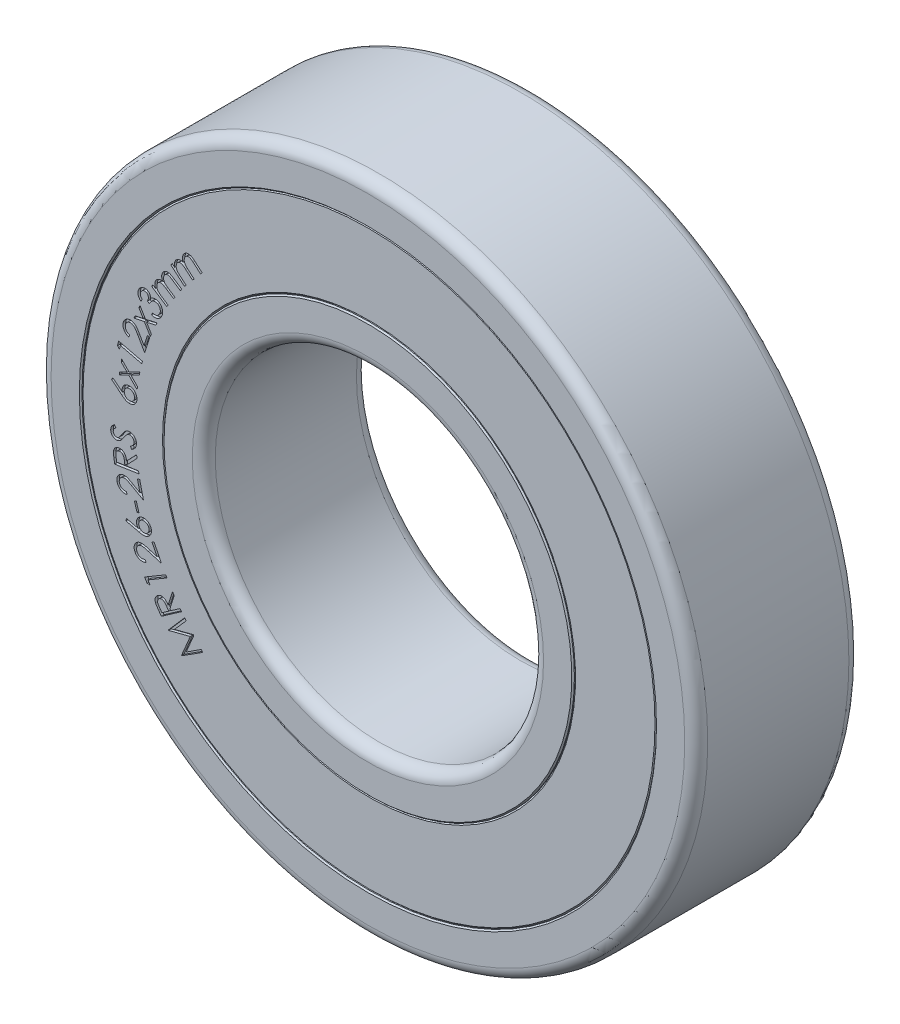
SolidWorks part; units mm, degrees
material "AISI 316 Annealed Stainless Steel Bar (SS)"
ref_plane "Front" through (0, 0, 0) normal (0, 0, 1) x (1, 0, 0)
ref_plane "Top" through (0, 0, 0) normal (0, 1, 0) x (1, 0, 0)
ref_plane "Right" through (0, 0, 0) normal (1, 0, 0) x (0, 0, -1)
sketch "LAYOUT R" plane through (0, 0, 0) normal (1, 0, 0) x (0, 0, -1)
  line L0 (-1.5, 3) -> (1.5, 3)
  line L1 (1.5, -6) -> (-1.5, -6) construction
  line L2 (1.5, -6) -> (1.5, 6) construction
  line L3 (1.5, 6) -> (-1.5, 6)
  line L4 (-1.5, -6) -> (-1.5, 6) construction
  line L5 (1.5, -6) -> (-1.5, 6) construction
  line L6 (1.5, 6) -> (-1.5, -6) construction
  line L7 (-1.5, 3.75) -> (1.5, 3.75)
  line L8 (-1.5, 5.25) -> (1.5, 5.25)
  line L11 (-17.5, 0) -> (17.5, 0) construction
  line L12 (-1.5, 6) -> (-1.5, 5.25)
  line L13 (1.5, 6) -> (1.5, 5.25)
  line L14 (-1.5, 5.25) -> (-1.5, 3.75)
  line L15 (1.5, 5.25) -> (1.5, 3.75)
  line L16 (-1.5, 3.75) -> (-1.5, 3)
  line L17 (1.5, 3.75) -> (1.5, 3)
  line L18 (-1.48, 5.25) -> (-1.48, 3.75)
  line L19 (1.48, 5.25) -> (1.48, 3.75)
  point P0 (0, 0)
  point P15 (0, 0)
  dimension "D1" = 3
  dimension "D2" = 12
  dimension "D3" = 3
  dimension "D6" = 0.02
  dimension "D7" = 0.02
  dimension "D4" = 3.75
  dimension "D5" = 5.25
sketch "Sketch R, INNER BODY" plane through (0, 0, 0) normal (1, 0, 0) x (0, 0, -1)
  line L0 (-1.5, 3) -> (1.5, 3) construction
  line L2 (-1.5, 3.75) -> (1.5, 3.75) construction
  line L4 (-1.5, 3) -> (1.5, 3)
  line L6 (-1.5, 3.75) -> (1.5, 3.75)
  line L8 (1.5, 3.75) -> (1.5, 3) construction
  line L9 (-1.5, 3.75) -> (-1.5, 3) construction
  line L10 (1.5, 3.75) -> (1.5, 3)
  line L11 (-1.5, 3.75) -> (-1.5, 3)
  line L12 (-17.5, 0) -> (17.5, 0) construction
  line L13 (-17.5, 0) -> (17.5, 0) construction
sketch "Sketch R, OUTER BODY" plane through (0, 0, 0) normal (1, 0, 0) x (0, 0, -1)
  line L2 (-1.5, 5.25) -> (1.5, 5.25) construction
  line L3 (1.5, 6) -> (-1.5, 6) construction
  line L6 (-1.5, 5.25) -> (1.5, 5.25)
  line L7 (1.5, 6) -> (-1.5, 6)
  line L8 (-17.5, 0) -> (17.5, 0) construction
  line L9 (-17.5, 0) -> (17.5, 0) construction
  line L10 (1.5, 6) -> (1.5, 5.25) construction
  line L11 (-1.5, 6) -> (-1.5, 5.25) construction
  line L12 (1.5, 6) -> (1.5, 5.25)
  line L13 (-1.5, 6) -> (-1.5, 5.25)
sketch "Sketch R, SEAL FACES" plane through (0, 0, 0) normal (1, 0, 0) x (0, 0, -1)
  line L0 (-17.5, 0) -> (17.5, 0) construction
  line L1 (-17.5, 0) -> (17.5, 0) construction
  line L3 (-1.5, 3.75) -> (1.5, 3.75) construction
  line L5 (-1.5, 5.25) -> (1.5, 5.25) construction
  line L7 (-1.48, 3.75) -> (1.48, 3.75)
  line L9 (-1.48, 5.25) -> (1.48, 5.25)
  line L10 (1.48, 5.25) -> (1.48, 3.75) construction
  line L11 (-1.48, 5.25) -> (-1.48, 3.75) construction
  line L12 (1.48, 5.25) -> (1.48, 3.75)
  line L13 (-1.48, 5.25) -> (-1.48, 3.75)
revolve "Revolve INNER BODY" add sketch "Sketch R, INNER BODY" angle 360 about L13
fillet "Fillet INNER BODY" radius 0.21 2 edges at (3, 0, 1.5) (3, 0, -1.5)
chamfer "Chamfer INNER BODY" distance 0.024 angle 45 2 edges at (3.75, 0, -1.5) (3.75, 0, 1.5)
revolve "Revolve OUTER BODY" add sketch "Sketch R, OUTER BODY" angle 360 about L9
fillet "Fillet OUTER BODY" radius 0.21 2 edges at (6, 0, -1.5) (6, 0, 1.5)
chamfer "Chamfer OUTER BODY" distance 0.024 angle 45 2 edges at (5.25, 0, 1.5) (5.25, 0, -1.5)
revolve "Revolve SEALS" add sketch "Sketch R, SEAL FACES" angle 360 about L1
chamfer "Chamfer SEALS" distance 0.024 angle 45 4 edges at (3.75, 0, -1.48) (5.25, 0, -1.48) (5.25, 0, 1.48) (3.75, 0, 1.48)
sketch "Sketch TEXT RADIUS 1 — MANUALLY ASSIGN TEXT AND FONT SIZE (FROM EQUATIONS)" plane through (0, 0, 1.48) normal (0, 0, 1) x (1, 0, 0)
  circle A0 centre (0, 0) radius 4.275 construction
  text T0 "MR126-2RS  6x12x3mm" font "Century Gothic" height 0.45
  dimension "D1" = 8.55
extrude "Cut-Extrude SEAL LABEL 1" cut sketch "Sketch TEXT RADIUS 1 — MANUALLY ASSIGN TEXT AND FONT SIZE (FROM EQUATIONS)" against normal blind 0.05
sketch "Sketch TEXT RADIUS 2 — MANUALLY ASSIGN TEXT AND FONT SIZE (FROM EQUATIONS)" plane through (0, 0, -1.48) normal (0, 0, -1) x (-1, 0, 0)
  circle A0 centre (0, 0) radius 4.275 construction
  text T0 "MR126-2RS  6x12x3mm" font "Century Gothic" height 0.45
  dimension "D1" = 8.55
extrude "Cut-Extrude SEAL LABEL 2" cut sketch "Sketch TEXT RADIUS 2 — MANUALLY ASSIGN TEXT AND FONT SIZE (FROM EQUATIONS)" against normal blind 0.05
equation "\"_i__BORE\"= 6"
equation "\"_i__OUTSIDE_DIAMETER\"= 12"
equation "\"_i__WIDTH\"= 3"
equation "\"_i_optional__TEXT_RADIUS_ADJUSTMENT\"= 0"
equation "\"_output__FONT_SIZE_mm\"= \"BODY_SPAN__SEAL__OF_RADIUS\" * \"param__FONT_SIZE_RATIO\"'MANUALLY ASSIGN TO FONT"
equation "\"BODY__HALF_WIDTH\"= \"_i__WIDTH\" / 2"
equation "\"BODY_SPAN___OF_DIAMETER\"= \"_i__OUTSIDE_DIAMETER\" - \"_i__BORE\""
equation "\"BODY_SPAN___OF_RADIUS\"= \"BODY_SPAN___OF_DIAMETER\" / 2"
equation "\"BODY_SPAN__BORE_AND_OD__OF RADIUS\"= ( \"BODY_SPAN___OF_RADIUS\" - \"BODY_SPAN__SEAL__OF_RADIUS\" ) / 2"
equation "\"BODY_SPAN__SEAL__OF_RADIUS\"= \"BODY_SPAN___OF_RADIUS\" * \"param__SEAL_PANEL_SPAN__RATIO_OF_BODY_RADIAN\""
equation "\"BORE__RADIUS\"= \"_i__BORE\" / 2"
equation "\"CORNER_RADII\"= \"_i__WIDTH\" * \"param__CORNER_RADII__ISO_MAX_RATIO_TO_WIDTH\""
equation "\"param__CORNER_RADII__ISO_MAX_RATIO_TO_WIDTH\"= 0.07'WHERE WIDTH IS LESS THAN DIAMETER"
equation "\"param__FONT_SIZE_RATIO\"= 0.3"
equation "\"param__SEAL_FACE_INSET__RATIO_OF_WIDTH\"= .01"
equation "\"param__SEAL_PANEL_SPAN__RATIO_OF_BODY_RADIAN\"= 0.5"
equation "\"param__SIDE_CHAMFERS__RATIO_TO_OD\"= 1 / 500"
equation "\"RING_INNER__OUTSIDE_RADIUS\"= \"BORE__RADIUS\" + \"BODY_SPAN__BORE_AND_OD__OF RADIUS\""
equation "\"RING_OUTER__OUTSIDE_RADIUS\"= ( \"_i__OUTSIDE_DIAMETER\" / 2 ) - \"BODY_SPAN__BORE_AND_OD__OF RADIUS\""
equation "\"SEAL_FACE_INSET\"= \"_i__WIDTH\" * \"param__SEAL_FACE_INSET__RATIO_OF_WIDTH\""
equation "\"SIDE_FACE_AND_SEAL_CHAMFERS\"= \"_i__OUTSIDE_DIAMETER\" * \"param__SIDE_CHAMFERS__RATIO_TO_OD\""
equation "\"TEXT_RADIUS\"= \"_i__BORE\" + ( \"BODY_SPAN___OF_DIAMETER\" / 2 ) - \"_output__FONT_SIZE_mm\" + \"_i_optional__TEXT_RADIUS_ADJUSTMENT\""
equation "\"D1@Chamfer INNER BODY\"=\"SIDE_FACE_AND_SEAL_CHAMFERS\""
equation "\"D1@Chamfer OUTER BODY\"=\"SIDE_FACE_AND_SEAL_CHAMFERS\""
equation "\"D1@Chamfer SEALS\"=\"SIDE_FACE_AND_SEAL_CHAMFERS\""
equation "\"D1@Fillet INNER BODY\"=\"CORNER_RADII\""
equation "\"D1@Fillet OUTER BODY\"=\"CORNER_RADII\""
equation "\"D1@LAYOUT R\"=\"_i__WIDTH\""
equation "\"D1@Sketch TEXT RADIUS 1 — MANUALLY ASSIGN TEXT AND FONT SIZE (FROM EQUATIONS)\" = \"TEXT_RADIUS\""
equation "\"D1@Sketch TEXT RADIUS 2 — MANUALLY ASSIGN TEXT AND FONT SIZE (FROM EQUATIONS)\" = \"TEXT_RADIUS\""
equation "\"D2@LAYOUT R\"=\"_i__OUTSIDE_DIAMETER\""
equation "\"D3@LAYOUT R\"=\"BORE__RADIUS\""
equation "\"D4@LAYOUT R\"=\"RING_INNER__OUTSIDE_RADIUS\""
equation "\"D5@LAYOUT R\"=\"RING_OUTER__OUTSIDE_RADIUS\""
